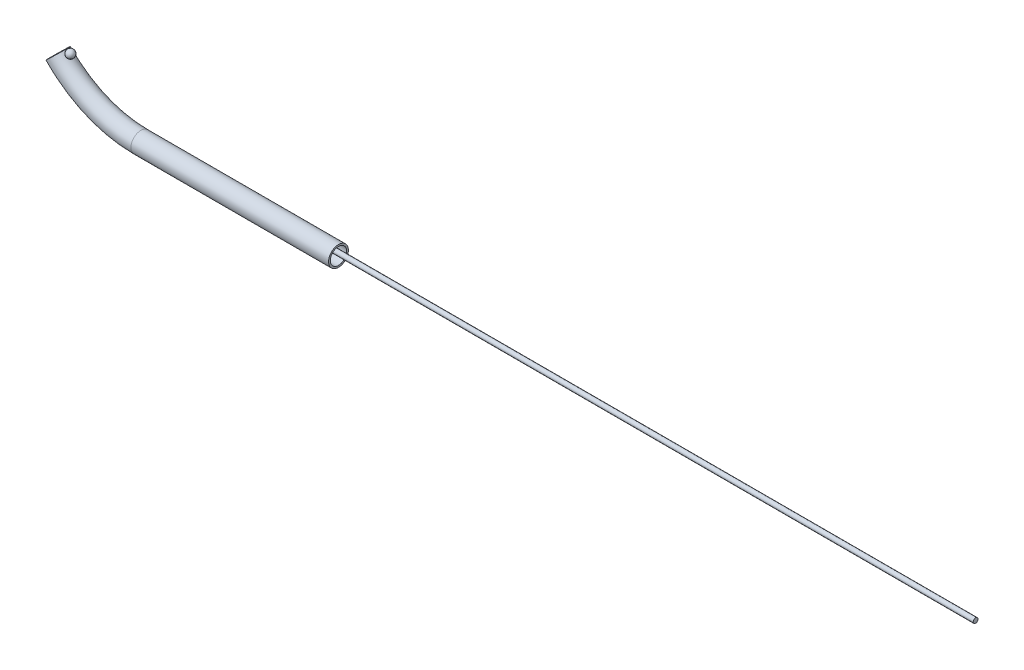
SolidWorks part; units mm, degrees
ref_plane "Front Plane" through (0, 0, 0) normal (0, 0, 1) x (1, 0, 0)
ref_plane "Top Plane" through (0, 0, 0) normal (0, 1, 0) x (1, 0, 0)
ref_plane "Right Plane" through (0, 0, 0) normal (1, 0, 0) x (0, 0, -1)
ref_axis "Axis1" through (-232.0518, 0, 0) along (1, 0, 0)
sketch "Sketch4" plane through (0, 0, 0) normal (0, 0, 1) x (1, 0, 0)
  line L0 (-218.053, 283.5718) -> (61.923, 683.419) construction
  line L1 (-68.365, 0) -> (-65.9542, 0)
  arc A0 (-68.365, 0) -> (-73.5499, 2.2253) centre (-68.365, 7.1532) cw
  point P2 (-73.5499, 2.2253)
  point P3 (-68.365, 0)
sketch "Sketch1" plane through (0, 0, 0) normal (1, 0, 0) x (0, 0, -1)
  circle A0 centre (0, 0) radius 0.61
  circle A1 centre (0, 0) radius 0.39
  dimension "D1" = 1.22
  dimension "D2" = 0.22
extrude "Boss-Extrude1" [suppressed] add sketch "Sketch1" along normal blind 10
ref_plane "Plane1" through (-65.9542, 0, 0) normal (1, 0, 0) x (0, 0, -1)
sketch "Sketch5" plane through (-65.9542, 0, 0) normal (1, 0, 0) x (0, 0, -1)
  circle A0 centre (0, 0) radius 0.6223
  circle A1 centre (0, 0) radius 0.5143
  dimension "D1" = 1.2446
  dimension "D2" = 1.0287
sweep "Sweep2" add profiles "Sketch5" path "Sketch4"
extrude "Boss-Extrude2" add sketch "Sketch5<2>" along normal blind 10
sketch "Sketch5<2>" plane through (-65.9542, 0, 0) normal (1, 0, 0) x (0, 0, -1) same geometry as "Sketch5"
sketch "Sketch6" plane through (0, 0, 0) normal (0, 0, 1) x (1, 0, 0)
  line L0 (-72.7874, 2.8286) -> (-72.7874, 2.3286) construction
  line L1 (-72.9491, 2.3879) -> (-72.6257, 2.7693)
  circle A0 centre (-72.7874, 2.5786) radius 0.25 construction
  arc A1 (-72.9491, 2.3879) -> (-72.6257, 2.7693) centre (-72.7874, 2.5786) ccw
  dimension "D1" = 0.5
revolve "Revolve2" add sketch "Sketch6" angle 360 about L1
sketch "Sketch7" plane through (0, 0, 0) normal (0, 0, 1) x (1, 0, 0)
  line L0 (-68.365, -0.6223) -> (-55.9542, -0.6223) construction
  line L1 (-68.365, -0.6223) -> (-55.9542, -0.6223) construction
  line L2 (-68.365, 0.1777) -> (-55.9542, 0.1777)
  arc A1 (-74.001, 1.7966) -> (-68.365, -0.6223) centre (-68.365, 7.1532) ccw construction
  arc A2 (-74.001, 1.7966) -> (-68.365, -0.6223) centre (-68.365, 7.1532) ccw construction
  arc A3 (-73.4211, 2.3477) -> (-68.365, 0.1777) centre (-68.365, 7.1532) ccw
  dimension "D1" = 0.8
sketch "Sketch8" plane through (-36.0182, 37.8966, 0) normal (-0.6889, 0.7248, 0) x (0.7248, 0.6889, 0)
  circle A0 centre (-51.6014, 0) radius 0.15
  point P0 (-51.6014, 0)
  dimension "D1" = 0.3
sweep "Sweep3" add profiles "Sketch8" path "Sketch7"
sketch "Sketch9" plane through (-55.9542, 0, 0) normal (1, 0, 0) x (0, 0, -1)
  circle A0 centre (0, 0.1777) radius 0.15 construction
  circle A1 centre (0, 0.1777) radius 0.15
extrude "Boss-Extrude3" add sketch "Sketch9" along normal blind 40
sketch "Sketch12" plane through (-15.9542, 0, 0) normal (1, 0, 0) x (0, 0, -1)
  line L0 (0.15, 0.1777) -> (-0.15, 0.1777)
  circle A0 centre (0, 0.1777) radius 0.15 construction
ref_plane "Plane2" through (0, 0.1777, 0) normal (0, 1, 0) x (0, 0, 1)
sketch "Sketch11" plane through (-15.9542, 0, 0) normal (1, 0, 0) x (0, 0, -1)
  circle A0 centre (0, 0.1777) radius 0.15 construction
  circle A1 centre (0, 0.1777) radius 0.15
sketch "Sketch10" plane through (-32.5249, 0.1777, -2.7436) normal (0, -1, 0) x (1, 0, 0)
  line L1 (18.717, 2.7436) -> (20.717, 2.7436)
  line L2 (18.717, 2.007) -> (18.717, 3.4802) construction
  line L3 (21.717, 1.7436) -> (21.717, -2.6379)
  arc A0 (21.717, 1.7436) -> (20.717, 2.7436) centre (20.717, 1.7436) ccw
  point P6 (21.717, 2.7436)
  dimension "D1" = 3
  dimension "D2" = 1
sweep "Sweep4" add profiles "Sketch11" path "Sketch10" rebuild error yes
equation "\"Do\"=8.5mm"
equation "\"Lo\"=10"
equation "\"screw_diam\"= 3.5mm"
equation "\"wheel_Do\"=12.5mm"
equation "\"wheel_thickness\"=4mm"
equation "\"Collet_diameter\"=4.3"
equation "\"clearance\"= 0.5mm"
equation "\"handle_body_width\"= 10mm"
equation "\"finger_diameter\"=35"
equation "\"collet_lid_diameter\"=10"
equation "\"screw_cap_diam\"=5.15"
equation "\"handle_thickness\"=12.5mm"
equation "\"post_hole_diam\"=2"
equation "\"roll_rod_diam\"= 6.5 "
equation "\"roll_rod_length\"=6.6"
equation "\"disc_diam\"=5"
equation "\"disc_width\"=1.5"
equation "\"arm_width\"=5"
equation "\"arm_thickness\"=4.5"
equation "\"wheel_total_diam\"=30"
equation "\"spring_diam\"=4.1"
equation "\"collet_length\"= 18.75mm"
equation "\"tip_length\"= 40mm"
equation "\"cable_tube_OD\"=0.508"
equation "\"cable_OD\"= 0.3mm"
equation "\"D1@Sketch8\"=\"cable_OD\""
